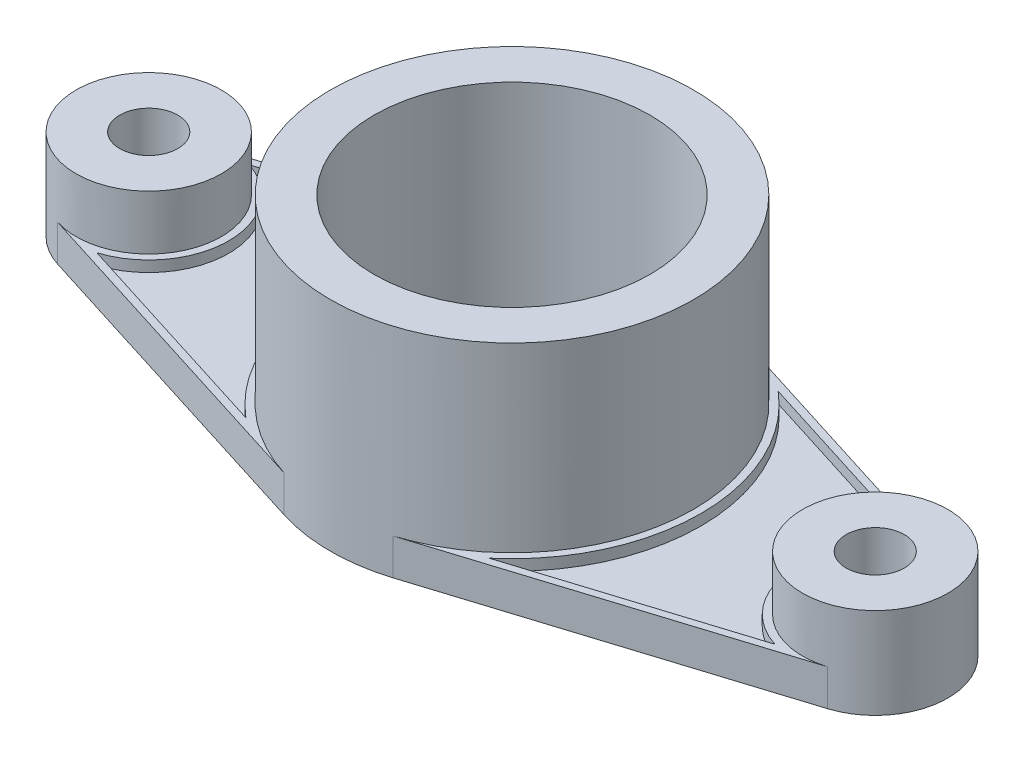
SolidWorks part; units mm, degrees
material "Polybutadiene (PB)"
ref_plane "Front Plane" through (0, 0, 0) normal (0, 0, 1) x (1, 0, 0)
ref_plane "Top Plane" through (0, 0, 0) normal (0, 1, 0) x (1, 0, 0)
ref_plane "Right Plane" through (0, 0, 0) normal (1, 0, 0) x (0, 0, -1)
sketch "Sketch1" plane through (0, 0, 0) normal (0, 1, 0) x (1, 0, 0)
  line L0 (2.6171, 0) -> (50002.6171, 0) construction
  line L1 (15, 47.697) -> (106, 19.0788)
  line L2 (15, -47.697) -> (106, -19.0788)
  line L3 (0, -2.9118) -> (0, -50002.9118) construction
  line L4 (-15, -47.697) -> (-106, -19.0788)
  line L5 (-15, 47.697) -> (-106, 19.0788)
  circle A0 centre (0, 0) radius 38
  circle A1 centre (100, 0) radius 20
  circle A2 centre (0, 0) radius 50
  circle A3 centre (100, 0) radius 8
  circle A4 centre (-100, 0) radius 8
  circle A5 centre (-100, 0) radius 20
  dimension "D1" = 12
  dimension "D2" = 12
  dimension "D3" = 76
  dimension "D4" = 40
  dimension "D5" = 200
extrude "Boss-Extrude1" add sketch "Sketch1" along normal blind 10 contours L5 A5 L4 A2 | A5 A4 | A2 A0 | A2 L2 A1 L1 | A1 A3 region at (62.9801, 0, 0) region at (39.1711, 0, -28.7437) region at (115.6684, 0, -11.4975) region at (-62.9801, 0, 0) region at (-88.5025, 0, -15.6684)
extrude "Boss-Extrude2" add sketch "Sketch1<3>" along normal blind 25 contours A5 A4 | A1 A3 region at (115.6684, 0, -11.4975) region at (-88.5025, 0, -15.6684)
sketch "Sketch1<3>" plane through (0, 0, 0) normal (0, 1, 0) x (1, 0, 0) same geometry as "Sketch1"
extrude "Boss-Extrude3" add sketch "Sketch1<4>" along normal blind 60 contours A2 A0 region at (39.1711, 0, -28.7437)
sketch "Sketch1<4>" plane through (0, 0, 0) normal (0, 1, 0) x (1, 0, 0) same geometry as "Sketch1"
sketch "Sketch5" plane through (0, 10, 0) normal (0, 1, 0) x (1, 0, 0)
  line L0 (0, 84.8144) -> (0, -102.1934) construction
  line L1 (-33.4788, -39.7891) -> (-93.3335, -20.9656)
  line L2 (-93.3335, 20.9656) -> (-33.4788, 39.7891)
  line L10 (93.3335, 20.9656) -> (33.4788, 39.7891)
  line L11 (33.4788, -39.7891) -> (93.3335, -20.9656)
  line L12 (93.3335, 20.9656) -> (33.4788, 39.7891)
  line L13 (33.4788, -39.7891) -> (93.3335, -20.9656)
  arc A0 (-93.3335, 20.9656) -> (-93.3335, -20.9656) centre (-100, 0) cw
  arc A1 (-33.4788, -39.7891) -> (-33.4788, 39.7891) centre (0, 0) cw
  arc A10 (33.4788, -39.7891) -> (33.4788, 39.7891) centre (0, 0) ccw
  arc A11 (93.3335, 20.9656) -> (93.3335, -20.9656) centre (100, 0) ccw
  arc A12 (33.4788, -39.7891) -> (33.4788, 39.7891) centre (0, 0) ccw
  arc A13 (93.3335, 20.9656) -> (93.3335, -20.9656) centre (100, 0) ccw
  dimension "D1" = 2
extrude "Cut-Extrude1" cut sketch "Sketch5" against normal blind 3
